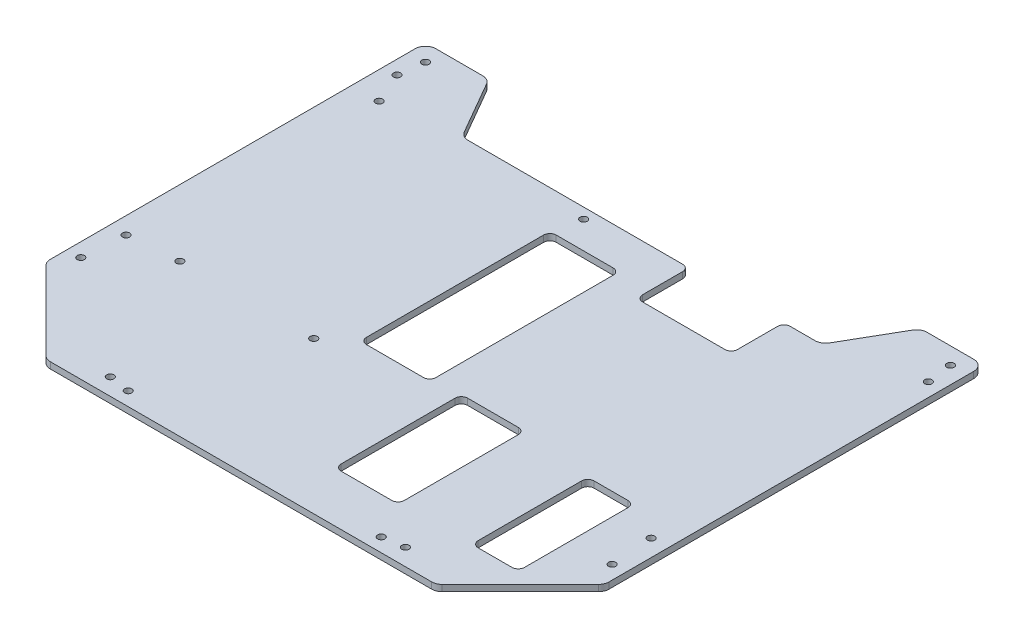
SolidWorks part; units mm, degrees
material "Acier non allié"
ref_plane "Front" through (0, 0, 0) normal (0, 0, 1) x (1, 0, 0)
ref_plane "Top" through (0, 0, 0) normal (0, 1, 0) x (1, 0, 0)
ref_plane "Right" through (0, 0, 0) normal (1, 0, 0) x (0, 0, -1)
sketch "Esquisse1" plane through (0, 0, 0) normal (0, 1, 0) x (1, 0, 0)
  line L0 (0, 0) -> (0, 1919.0564) construction
  line L1 (-92.5, 0) -> (92.5, 0)
  line L2 (92.5, 0) -> (132.5, 40)
  line L3 (132.5, 40) -> (132.5, 220)
  line L4 (132.5, 220) -> (102.5, 220)
  line L5 (102.5, 220) -> (85.1795, 190)
  line L6 (85.1795, 190) -> (-85.1795, 190)
  line L7 (-102.5, 220) -> (-85.1795, 190)
  line L8 (-132.5, 220) -> (-102.5, 220)
  line L9 (-132.5, 40) -> (-132.5, 220)
  line L10 (-92.5, 0) -> (-132.5, 40)
  point P12 (0, 190)
  dimension "D1" = 132.5
  dimension "D2" = 220
  dimension "D3" = 30
  dimension "D4" = 30
  dimension "D5" = 40
  dimension "D6" = 40
  dimension "D7" = 60
extrude "Boss.-Extru.1" add sketch "Esquisse1" along normal blind 3
fillet "Congé1" radius 5 10 edges at (132.5, 1.5, -220) (102.5, 1.5, -220) (85.1795, 1.5, -190) (-85.1795, 1.5, -190) (-102.5, 1.5, -220) (-132.5, 1.5, -220) (-132.5, 1.5, -40) (-92.5, 1.5, 0) (92.5, 1.5, 0) (132.5, 1.5, -40)
sketch "Esquisse2" plane through (0, 0, 0) normal (0, -1, 0) x (1, 0, 0)
  line L0 (0, 0) -> (0, -330.9968) construction
  line L1 (-90.4289, 0) -> (90.4289, 0) construction
  line L2 (-105.3868, -220) -> (-127.5, -220) construction
  line L3 (-132.5, -215) -> (-132.5, -42.0711) construction
  line L4 (-90.4289, 0) -> (90.4289, 0) construction
  line L5 (132.5, -42.0711) -> (132.5, -215) construction
  line L6 (-119.5, -185) -> (-22.5, -185) construction
  line L7 (82.2927, -190) -> (-82.2927, -190) construction
  line L8 (-132.5, -215) -> (-132.5, -42.0711) construction
  line L9 (-101, -72) -> (-37.5, -72) construction
  circle A0 centre (-70, -8) radius 1
  circle A1 centre (-124.5, -70) radius 1
  circle A2 centre (-124.5, -212) radius 1
  circle A3 centre (124.5, -212) radius 1
  circle A4 centre (124.5, -70) radius 1
  circle A5 centre (70, -8) radius 1
  circle A6 centre (126, -50) radius 1.5
  circle A7 centre (126, -200) radius 1.5
  circle A8 centre (-60, -6.5) radius 1.5
  circle A9 centre (60, -6.5) radius 1.5
  circle A10 centre (-126, -50) radius 1.5
  circle A11 centre (-126, -200) radius 1.5
  circle A12 centre (-119.5, -185) radius 1.5
  circle A13 centre (-22.5, -185) radius 1.5
  circle A14 centre (-101, -72) radius 1.5
  circle A15 centre (-37.5, -72) radius 1.5
  dimension "D3" = 2
  dimension "D6" = 2
  dimension "D9" = 2
  dimension "D12" = 3
  dimension "D15" = 3
  dimension "D16" = 3
  dimension "D17" = 3
  dimension "D24" = 3
  dimension "D27" = 3
  dimension "D31" = 3
  dimension "D32" = 3
  dimension "D36" = 3
  dimension "D37" = 3
  dimension "D1" = 70
  dimension "D2" = 8
  dimension "D4" = 124.5
  dimension "D5" = 70
  dimension "D7" = 8
  dimension "D8" = 8
  dimension "D10" = 50
  dimension "D11" = 6.5
  dimension "D13" = 15
  dimension "D14" = 6.5
  dimension "D18" = 10
  dimension "D19" = 6.5
  dimension "D20" = 6.5
  dimension "D21" = 10
  dimension "D22" = 50
  dimension "D23" = 6.5
  dimension "D25" = 15
  dimension "D26" = 6.5
  dimension "D28" = 97
  dimension "D29" = 5
  dimension "D30" = 13
  dimension "D33" = 63.5
  dimension "D34" = 113
  dimension "D35" = 18.5
extrude "Enlèv. mat.-Extru.1" cut sketch "Esquisse2" against normal through all
hole_wizard "Dégagement M31" positions "Esquisse3" profile "Esquisse4" hole size "M3" standard "ISO" end condition through all
sketch "Esquisse3" plane through (0, 0, 0) normal (0, -1, 0) x (-1, 0, 0)
  point P0 (-70, 8)
  point P3 (-124.5, 70)
  point P6 (-124.5, 212)
  point P9 (124.5, 212)
  point P12 (124.5, 70)
  point P15 (70, 8)
  point P18 (-126, 200)
  point P21 (-126, 50)
  point P24 (-60, 6.5)
  point P27 (60, 6.5)
  point P44 (126, 50)
  point P49 (126, 200)
  point P52 (101, 72)
  point P55 (37.5, 72)
  point P58 (119.5, 185)
  point P61 (22.5, 185)
sketch "Esquisse4" plane through (70, 0, -8) normal (1, 0, 0) x (0, 0, -1)
  line L0 (0, 0) -> (0, 3)
  line L1 (0, 3) -> (1.7, 3)
  line L2 (1.7, 3) -> (1.7, 0)
  line L5 (1.7, 0) -> (0, 0)
  line L11 (0, -6.35) -> (0, 107.95) construction
  dimension "Diamètre du perçage jusqu'au prochain" = 3.4
  dimension "Profondeur du perçage jusqu'au prochain" = 3
sketch "Esquisse5" plane through (0, 0, 0) normal (0, -1, 0) x (1, 0, 0)
  line L6 (82.2927, -190) -> (-82.2927, -190) construction
  line L7 (22.5, -190) -> (67.5, -190)
  line L20 (22.5, -190) -> (22.5, -165)
  line L21 (22.5, -165) -> (67.5, -165)
  line L22 (67.5, -190) -> (67.5, -165)
  line L23 (132.5, -42.0711) -> (132.5, -215) construction
  line L25 (-25.5, -172) -> (7.5, -172)
  line L26 (-25.5, -172) -> (-25.5, -82)
  line L27 (-25.5, -82) -> (7.5, -82)
  line L28 (7.5, -172) -> (7.5, -82)
  line L29 (-132.5, -215) -> (-132.5, -42.0711) construction
  line L30 (127.5, -220) -> (105.3868, -220) construction
  line L31 (84.5, -80) -> (106.5, -80)
  line L32 (84.5, -80) -> (84.5, -25)
  line L33 (84.5, -25) -> (106.5, -25)
  line L34 (106.5, -80) -> (106.5, -25)
  line L35 (-90.4289, 0) -> (90.4289, 0) construction
  line L38 (20.5, -84) -> (50.5, -84)
  line L39 (20.5, -84) -> (20.5, -24)
  line L40 (20.5, -24) -> (50.5, -24)
  line L41 (50.5, -84) -> (50.5, -24)
  dimension "D14" = 24
  dimension "D12" = 60
  dimension "D1" = 65
  dimension "D2" = 110
  dimension "D3" = 25
  dimension "D4" = 82
  dimension "D5" = 140
  dimension "D6" = 90
  dimension "D7" = 33
  dimension "D8" = 48
  dimension "D9" = 140
  dimension "D10" = 55
  dimension "D11" = 22
  dimension "D13" = 30
  dimension "D15" = 82
extrude "Enlèv. mat.-Extru.2" cut sketch "Esquisse5" against normal through all
fillet "Congé2" radius 3 16 edges at (67.5, 1.5, -190) (67.5, 1.5, -165) (22.5, 1.5, -165) (22.5, 1.5, -190) (106.5, 1.5, -80) (84.5, 1.5, -80) (84.5, 1.5, -25) (106.5, 1.5, -25) (7.5, 1.5, -82) (7.5, 1.5, -172) (-25.5, 1.5, -82) (-25.5, 1.5, -172) (50.5, 1.5, -84) (20.5, 1.5, -84) (50.5, 1.5, -24) (20.5, 1.5, -24)
equation "\"WIDTH\"= 300mm'Total width of the robot"
equation "\"LENGTH\"= 220mm'Total length of the robot"
equation "\"CUT_DEPTH\"= 45mm'Depth of the cut on the edges of the plate"
equation "\"Plate_th\"= 3mm'Thickness of the plate"
equation "\"D1\"= \"Plate_th\""
